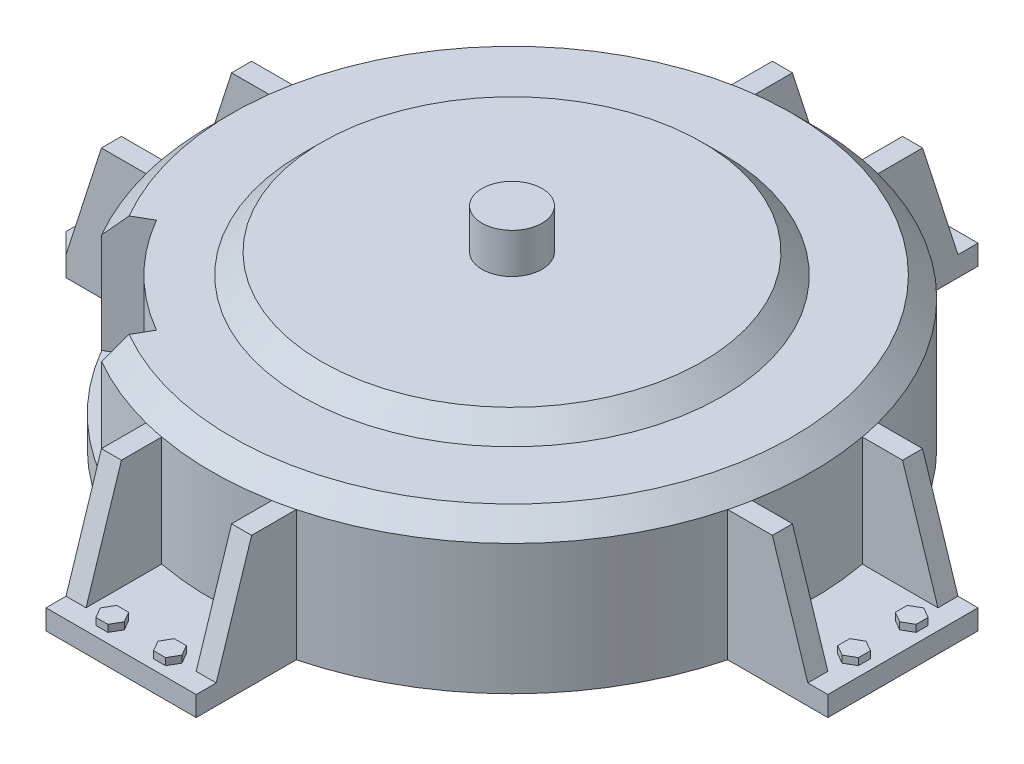
SolidWorks part; units mm, degrees
ref_plane "Front Plane" through (0, 0, 0) normal (0, 0, 1) x (1, 0, 0)
ref_plane "Top Plane" through (0, 0, 0) normal (0, 1, 0) x (1, 0, 0)
ref_plane "Right Plane" through (0, 0, 0) normal (1, 0, 0) x (0, 0, -1)
sketch "Sketch1" plane through (0, 0, 0) normal (0, 1, 0) x (1, 0, 0)
  circle A0 centre (0, 0) radius 150
  dimension "D1" = 300
extrude "Boss-Extrude1" add sketch "Sketch1" along normal blind 75
chamfer "Chamfer1" distance 10 angle 45 1 edges at (0, 75, 150)
sketch "Sketch2" plane through (0, 0, 0) normal (0, -1, 0) x (1, 0, 0)
  line L1 (-145.2369, -37.5) -> (-195.2369, -37.5)
  line L3 (-145.2369, 37.5) -> (-195.2369, 37.5)
  line L4 (-195.2369, -37.5) -> (-195.2369, 37.5)
  line L5 (-150, 0) -> (-195.2369, 37.5) construction
  line L6 (-150, 0) -> (-195.2369, -37.5) construction
  circle A0 centre (0, 0) radius 150 construction
  circle A1 centre (0, 0) radius 150
  point P0 (-150, 0)
  circle M6 centre (0, 0) radius 150
  dimension "D1" = 75
  dimension "D2" = 50
extrude "Boss-Extrude2" add sketch "Sketch2" against normal blind 10 contours L4 L1 L3 M6 region at (-171.8083, 0, 0)
chamfer "Chamfer2" distance 10 angle 45 2 edges at (-195.2369, 5, -37.5) (-195.2369, 5, 37.5)
sketch "Sketch3" plane through (0, 0, 37.5) normal (0, 0, 1) x (1, 0, 0)
  line L0 (-145.2369, 10) -> (-145.2369, 65)
  line L1 (-150, 65) -> (150, 65) construction
  line L2 (-145.2369, 65) -> (-167.5569, 65)
  line L3 (-167.5569, 65) -> (-185.2369, 10)
  line L4 (-185.2369, 10) -> (-145.2369, 10)
  line L5 (-185.2369, 10) -> (-185.2369, 0) construction
  line L6 (-145.2369, 10) -> (-185.2369, 10) construction
  dimension "D1" = 17.68
extrude "Boss-Extrude3" add sketch "Sketch3" against normal blind 10
sketch "Sketch4" plane through (0, 10, 0) normal (0, 1, 0) x (1, 0, 0)
  line L0 (-185.2369, 37.5) -> (-185.2369, -66.2856) construction
  line L2 (-180.0407, -17.3928) -> (-180.0407, -11.3928)
  line L3 (-180.0407, -11.3928) -> (-185.2369, -8.3928)
  line L4 (-185.2369, -8.3928) -> (-190.433, -11.3928)
  line L5 (-190.433, -11.3928) -> (-190.433, -17.3928)
  line L6 (-190.433, -17.3928) -> (-185.2369, -20.3928)
  line L7 (-185.2369, -20.3928) -> (-180.0407, -17.3928)
  circle A0 centre (-185.2369, -14.3928) radius 5.1962 construction
  dimension "D1" = 6
extrude "Boss-Extrude4" add sketch "Sketch4" along normal blind 3.5
mirror "Mirror1" about plane through (0, 0, 0) normal (0, 0, 1) of "Boss-Extrude4", "Boss-Extrude3"
pattern_circular "CirPattern1" count 4 over 360 about axis through (0, 0, 0) along (0, 1, 0) of "Mirror1", "Boss-Extrude2", "Boss-Extrude3"
sketch "Sketch5" plane through (0, 75, 0) normal (0, 1, 0) x (1, 0, 0)
  line L2 (-65, -112.5833) -> (-75, -129.9038)
  line L3 (-112.5833, -65) -> (-129.9038, -75)
  arc A0 (-112.5833, -65) -> (-65, -112.5833) centre (0, 0) ccw
  arc A1 (-145.2369, -37.5) -> (-37.5, -145.2369) centre (0, 0) ccw construction
  arc A2 (-129.9038, -75) -> (-75, -129.9038) centre (0, 0) ccw
  dimension "D3" = 260
extrude "Cut-Extrude1" cut sketch "Sketch5" against normal blind 60
sketch "Sketch6" plane through (0, 75, 0) normal (0, 1, 0) x (1, 0, 0)
  circle A0 centre (0, 0) radius 110
  dimension "D1" = 220
extrude "Boss-Extrude6" add sketch "Sketch6" along normal blind 10
chamfer "Chamfer3" distance 15 angle 45 1 edges at (0, 85, 110)
sketch "Sketch7" plane through (0, 85, 0) normal (0, 1, 0) x (1, 0, 0)
  circle A0 centre (0, 0) radius 15
  dimension "D1" = 30
extrude "Boss-Extrude7" add sketch "Sketch7" along normal blind 20
